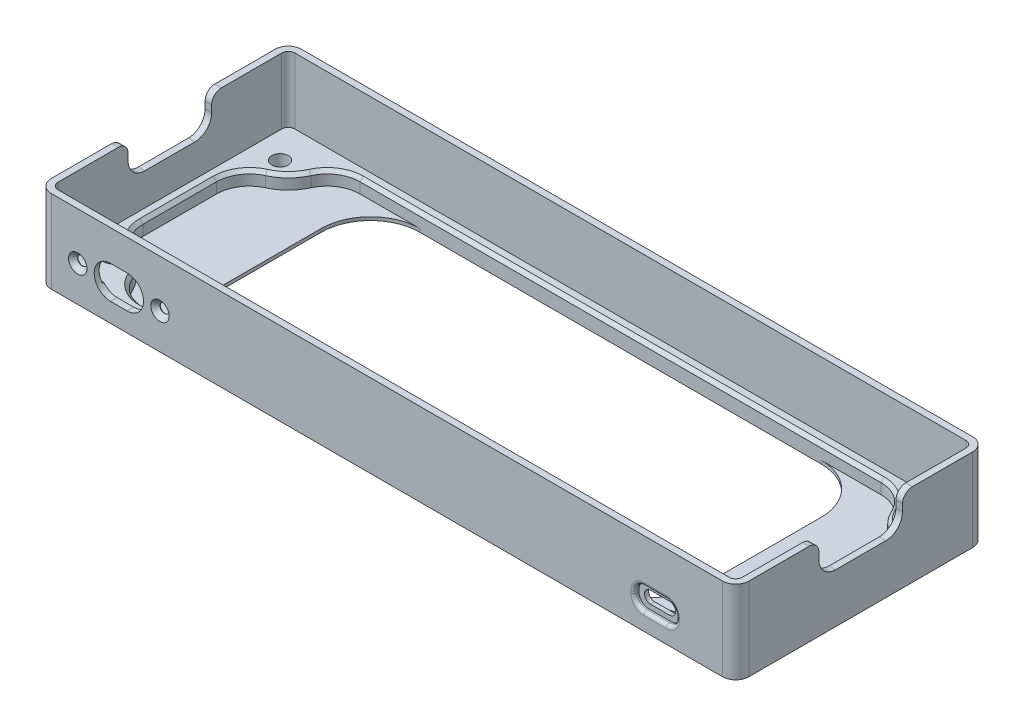
SolidWorks part; units mm, degrees
ref_plane "Front Plane" through (0, 0, 0) normal (0, 0, 1) x (1, 0, 0)
ref_plane "Top Plane" through (0, 0, 0) normal (0, 1, 0) x (1, 0, 0)
ref_plane "Right Plane" through (0, 0, 0) normal (1, 0, 0) x (0, 0, -1)
sketch "Sketch1" plane through (0, 0, 0) normal (0, 1, 0) x (1, 0, 0)
  line L1 (-102, -38) -> (102, -38)
  line L2 (-106, -34) -> (-106, 34)
  line L3 (-102, 38) -> (102, 38)
  line L4 (106, -34) -> (106, 34)
  line L5 (-106, -38) -> (106, 38) construction
  line L6 (-106, 38) -> (106, -38) construction
  line L7 (-101, -33) -> (101, -33)
  line L8 (-101, -33) -> (-101, 33)
  line L9 (-101, 33) -> (101, 33)
  line L10 (101, -33) -> (101, 33)
  line L11 (-101, -33) -> (101, 33) construction
  line L12 (-101, 33) -> (101, -33) construction
  arc A0 (-87, 33) -> (-101, 19) centre (-101, 33) cw
  arc A1 (-87, -33) -> (-101, -19) centre (-101, -33) ccw
  arc A2 (101, -19) -> (87, -33) centre (101, -33) ccw
  arc A3 (101, 19) -> (87, 33) centre (101, 33) cw
  arc A4 (102, 38) -> (106, 34) centre (102, 34) cw
  arc A5 (102, -38) -> (106, -34) centre (102, -34) ccw
  arc A6 (-102, -38) -> (-106, -34) centre (-102, -34) cw
  arc A7 (-106, 34) -> (-102, 38) centre (-102, 34) cw
  point P0 (0, 0)
  point P5 (0, 0)
  dimension "D5" = 14
  dimension "D6" = 4
  dimension "D1" = 212
  dimension "D2" = 76
  dimension "D3" = 5
  dimension "D4" = 5
extrude "Boss-Extrude1" add sketch "Sketch1" along normal blind 5.2 contours L1 L4 L3 L2 L10 L7 L8 L9 | A0 L9 L8 | L7 A1 L8 | L10 A2 L7 | A3 L10 L9 region at (-103.2359, 0, 35.2359) region at (-95.0582, 0, 27.0582) region at (95.0582, 0, 27.0582) region at (-95.0582, 0, -27.0582) region at (95.0582, 0, -27.0582)
fillet "Fillet1" radius 10 8 edges at (87, 2.6, 33) (101, 2.6, 19) (101, 2.6, -19) (87, 2.6, -33) (-87, 2.6, 33) (-101, 2.6, 19) (-87, 2.6, -33) (-101, 2.6, -19)
sketch "Sketch3" plane through (0, 0, 0) normal (0, -1, 0) x (-1, 0, 0)
  line L0 (102, 38) -> (-102, 38) construction
  line L1 (-102, -38) -> (-76, -38)
  line L2 (-106, -34) -> (-106, 34)
  line L3 (-102, 38) -> (-76, 38)
  line L4 (-76, -38) -> (-76, 38)
  line L5 (102, -38) -> (-102, -38) construction
  line L6 (102, -38) -> (76, -38)
  line L7 (106, -34) -> (106, 34)
  line L8 (102, 38) -> (76, 38)
  line L9 (76, -38) -> (76, 38)
  arc A0 (106, 34) -> (102, 38) centre (102, 34) ccw
  arc A1 (102, -38) -> (106, -34) centre (102, -34) ccw
  arc A2 (-102, -38) -> (-106, -34) centre (-102, -34) cw
  arc A3 (-106, 34) -> (-102, 38) centre (-102, 34) cw
  point P26 (106, -38)
  point P29 (-106, -38)
  dimension "D5" = 4
  dimension "D1" = 30
  dimension "D2" = 30
  dimension "D3" = 76
  dimension "D4" = 76
extrude "Boss-Extrude2" add sketch "Sketch3" against normal blind 1
sketch "Sketch2" plane through (0, 5.2, 0) normal (0, 1, 0) x (1, 0, 0)
  line L0 (-102, 38) -> (102, 38) construction
  line L1 (-106, -34) -> (-106, 34) construction
  line L2 (0, -11.44) -> (0, 11.44) construction
  line L3 (-11.44, 0) -> (11.44, 0) construction
  circle A0 centre (-96, 25.5) radius 2.5
  circle A1 centre (96, 25.5) radius 2.5
  circle A2 centre (96, -25.5) radius 2.5
  circle A3 centre (-96, -25.5) radius 2.5
  dimension "D1" = 12.5
  dimension "D3" = 5
  dimension "D2" = 10
extrude "Cut-Extrude1" cut sketch "Sketch2" against normal blind 5.2
sketch "Sketch4" plane through (0, 5.2, 0) normal (0, 1, 0) x (1, 0, 0)
  line L1 (-102, 38) -> (102, 38)
  line L2 (-106, 34) -> (-106, -34)
  line L3 (-102, -38) -> (102, -38)
  line L4 (106, 34) -> (106, -34)
  line L5 (102, -36) -> (-102, -36)
  line L6 (104, -34) -> (104, 34)
  line L7 (102, 36) -> (-102, 36)
  line L8 (-104, -34) -> (-104, 34)
  arc A0 (-102, -36) -> (-104, -34) centre (-102, -34) cw
  arc A1 (102, -36) -> (104, -34) centre (102, -34) ccw
  arc A2 (104, 34) -> (102, 36) centre (102, 34) ccw
  arc A3 (-102, 36) -> (-104, 34) centre (-102, 34) ccw
  arc A4 (102, 38) -> (106, 34) centre (102, 34) cw
  arc A5 (102, -38) -> (106, -34) centre (102, -34) ccw
  arc A6 (-106, -34) -> (-102, -38) centre (-102, -34) ccw
  arc A7 (-102, 38) -> (-106, 34) centre (-102, 34) ccw
  point P23 (106, -38)
  point P28 (-106, 38)
  dimension "D5" = 2
  dimension "D6" = 4
  dimension "D1" = 2
  dimension "D2" = 2
  dimension "D3" = 2
  dimension "D4" = 2
  dimension "D7" = 106
  dimension "D8" = 38
  dimension "D9" = 38
  dimension "D10" = 106
extrude "Boss-Extrude3" add sketch "Sketch4" along direction (0, 1, 0) on the side of the normal blind 20 contours L2 A6 L3 A5 L4 A4 L1 A7 | L6 A2 L7 A3 L8 A0 L5 A1
sketch "Sketch7" plane through (0, 0, 36) normal (0, 0, -1) x (-1, 0, 0)
  line L1 (-89.39, 15.2) -> (-73.61, 15.2)
  line L2 (-89.39, 15.2) -> (-89.39, 5.2)
  line L3 (-89.39, 5.2) -> (-73.61, 5.2)
  line L4 (-73.61, 15.2) -> (-73.61, 5.2)
  line L5 (-102, 5.2) -> (102, 5.2) construction
  line L6 (-106, 25.2) -> (-106, 0) construction
  dimension "D1" = 16.61
  dimension "D2" = 15.78
  dimension "D3" = 10
extrude "Boss-Extrude5" add sketch "Sketch7" along normal blind 0.75
sketch "Sketch6" plane through (0, 0, 38) normal (0, 0, 1) x (1, 0, 0)
  line L0 (84.39, 10.34) -> (78.61, 10.34)
  line L1 (74.28, 6.68) -> (88.72, 6.68) construction
  line L2 (74.28, 6.68) -> (74.28, 10.34) construction
  line L3 (74.28, 10.34) -> (88.72, 10.34) construction
  line L4 (88.72, 6.68) -> (88.72, 10.34) construction
  line L5 (74.28, 6.68) -> (88.72, 10.34) construction
  line L6 (74.28, 10.34) -> (88.72, 6.68) construction
  line L7 (106, 25.2) -> (106, 0) construction
  line L9 (78.61, 6.68) -> (84.39, 6.68)
  line L10 (-102, 0) -> (102, 0) construction
  arc A0 (78.61, 10.34) -> (78.61, 6.68) centre (78.61, 8.51) ccw
  arc A1 (84.39, 10.34) -> (84.39, 6.68) centre (84.39, 8.51) cw
  point P0 (81.5, 8.51)
  dimension "D1" = 24.5
  dimension "D2" = 14.44
  dimension "D3" = 8.51
  dimension "D4" = 3.66
  dimension "D5" = 2.89
  dimension "D6" = 2.89
extrude "Cut-Extrude2" cut sketch "Sketch6" against normal blind 10
sketch "Sketch8" plane through (0, 0, 38) normal (0, 0, 1) x (1, 0, 0)
  line L0 (84.39, 10.34) -> (78.61, 10.34) construction
  line L1 (78.11, 11.84) -> (84.89, 11.84)
  line L2 (75.11, 8.84) -> (75.11, 8.18)
  line L3 (78.11, 5.18) -> (84.89, 5.18)
  line L4 (87.89, 8.84) -> (87.89, 8.18)
  line L5 (78.61, 6.68) -> (84.39, 6.68) construction
  arc A0 (84.39, 6.68) -> (84.39, 10.34) centre (84.39, 8.51) ccw construction
  arc A1 (78.61, 10.34) -> (78.61, 6.68) centre (78.61, 8.51) ccw construction
  arc A2 (84.89, 11.84) -> (87.89, 8.84) centre (84.89, 8.84) cw
  arc A3 (84.89, 5.18) -> (87.89, 8.18) centre (84.89, 8.18) ccw
  arc A4 (75.11, 8.18) -> (78.11, 5.18) centre (78.11, 8.18) ccw
  arc A5 (78.11, 11.84) -> (75.11, 8.84) centre (78.11, 8.84) ccw
  dimension "D3" = 3.5
  dimension "D4" = 3.5
  dimension "D5" = 3
  dimension "D1" = 1.5
  dimension "D2" = 1.5
extrude "Cut-Extrude3" cut sketch "Sketch8" against normal blind 1.5
fillet "Fillet6" radius 1 8 edges at (87.89, 8.51, 38) (87.0113, 6.0587, 38) (81.5, 5.18, 38) (75.9887, 6.0587, 38) (75.11, 8.51, 38) (75.9887, 10.9613, 38) (81.5, 11.84, 38) (87.0113, 10.9613, 38)
chamfer "Chamfer1" distance 1 angle 45 2 edges at (89.39, 10.2, 35.25) (73.61, 10.2, 35.25)
sketch "Sketch9" plane through (0, 0, 38) normal (0, 0, 1) x (1, 0, 0)
  line L0 (-84, 10.81) -> (-79, 10.81) construction
  line L1 (-84, 15.81) -> (-79, 15.81)
  line L2 (-84, 5.81) -> (-79, 5.81)
  line L3 (-102, 0) -> (102, 0) construction
  line L4 (-106, 25.2) -> (-106, 0) construction
  arc A0 (-84, 15.81) -> (-84, 5.81) centre (-84, 10.81) ccw
  arc A1 (-79, 5.81) -> (-79, 15.81) centre (-79, 10.81) ccw
  point P2 (-81.5, 10.81)
  dimension "D3" = 5
  dimension "D1" = 10.81
  dimension "D2" = 5
  dimension "D4" = 24.5
extrude "Cut-Extrude4" cut sketch "Sketch9" against normal blind 3
sketch "Sketch11" plane through (0, 0, 38) normal (0, 0, 1) x (1, 0, 0)
  line L0 (-79, 15.81) -> (-84, 15.81) construction
  circle A0 centre (-94, 10.81) radius 1.4
  circle A1 centre (-69, 10.81) radius 1.4
  arc A2 (-84, 15.81) -> (-84, 5.81) centre (-84, 10.81) ccw construction
  dimension "D3" = 2.8
  dimension "D1" = 25
  dimension "D2" = 5
  dimension "D4" = 10
extrude "Cut-Extrude5" cut sketch "Sketch11" against normal blind 3.5
chamfer "Chamfer2" distance 1.4 angle 45 2 edges at (-67.6, 10.81, 38) (-92.6, 10.81, 38)
sketch "Sketch12" plane through (0, 0, 36) normal (0, 0, -1) x (-1, 0, 0)
  line L0 (69, 10.81) -> (94, 10.81) construction
  line L1 (69, 13.81) -> (94, 13.81)
  line L2 (69, 7.81) -> (94, 7.81)
  arc A0 (69, 13.81) -> (69, 7.81) centre (69, 10.81) ccw
  arc A1 (94, 7.81) -> (94, 13.81) centre (94, 10.81) ccw
  point P2 (81.5, 10.81)
  dimension "D1" = 3
extrude "Cut-Extrude6" cut sketch "Sketch12" against normal blind 0.5
chamfer "Chamfer3" distance 1 angle 45 16 edges at (-99.4163, 5.2, -16.5832) (-91.1005, 5.2, -23.1005) (-101, 5.2, 0) (-84.5832, 5.2, -31.4163) (-99.4163, 5.2, 16.5832) (0, 5.2, -33) (-91.1005, 5.2, 23.1005) (84.5832, 5.2, -31.4163) (-84.5832, 5.2, 31.4163) (91.1005, 5.2, -23.1005) (0, 5.2, 33) (99.4163, 5.2, -16.5832) (84.5832, 5.2, 31.4163) (101, 5.2, 0) (91.1005, 5.2, 23.1005) (99.4163, 5.2, 16.5832)
sketch "Sketch13" plane through (106, 0, 0) normal (1, 0, 0) x (0, 0, -1)
  line L0 (34, 25.2) -> (-34, 25.2) construction
  line L1 (-12.7, 15) -> (12.7, 15)
  line L2 (-12.7, 15) -> (-12.7, 25.2)
  line L3 (-12.7, 25.2) -> (12.7, 25.2)
  line L4 (12.7, 15) -> (12.7, 25.2)
  line L5 (-12.7, 15) -> (12.7, 25.2) construction
  line L6 (-12.7, 25.2) -> (12.7, 15) construction
  point P0 (0, 20.1)
  dimension "D1" = 5.1
  dimension "D2" = 25.4
extrude "Cut-Extrude7" cut sketch "Sketch13" against normal through all
fillet "Fillet7" radius 5.1 4 edges at (-105, 15, 12.7) (-105, 15, -12.7) (105, 15, -12.7) (105, 15, 12.7)
fillet "Fillet8" radius 3 4 edges at (-105, 25.2, 12.7) (-105, 25.2, -12.7) (105, 25.2, 12.7) (105, 25.2, -12.7)
fillet "Fillet9" radius 15 4 edges at (-76, 0.5, -33) (76, 0.5, -33) (76, 0.5, 33) (-76, 0.5, 33)
